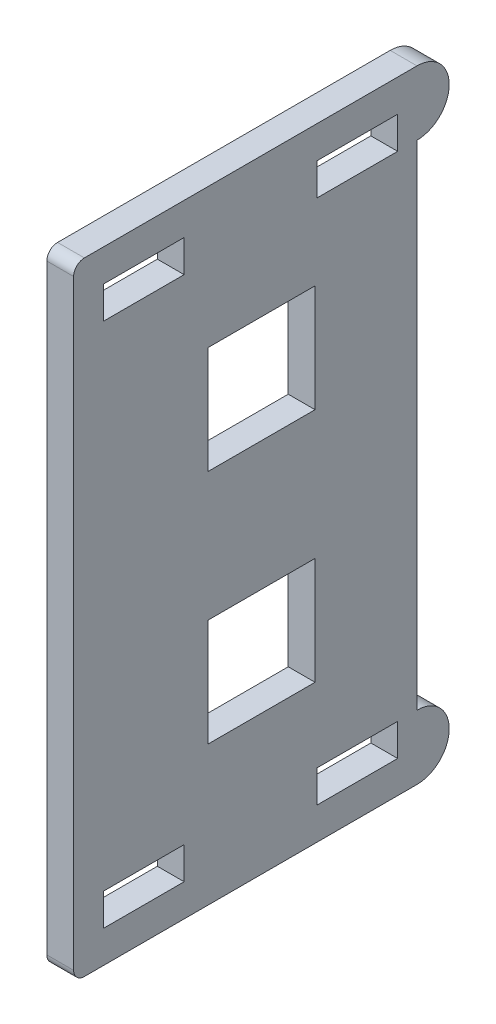
SolidWorks part; units mm, degrees
ref_plane "前视" through (0, 0, 0) normal (0, 0, 1) x (1, 0, 0)
ref_plane "上视" through (0, 0, 0) normal (0, 1, 0) x (1, 0, 0)
ref_plane "右视" through (0, 0, 0) normal (1, 0, 0) x (0, 0, -1)
sketch "草图2" plane through (0, 0, 0) normal (1, 0, 0) x (0, 0, -1)
  line L1 (-17.5, 29) -> (17.5, 29)
  line L2 (-17.5, 29) -> (-17.5, -29)
  line L3 (-17.5, -29) -> (17.5, -29)
  line L4 (17.5, 29) -> (17.5, -29)
  line L5 (-17.5, 29) -> (17.5, -29) construction
  line L6 (-17.5, -29) -> (17.5, 29) construction
  point P0 (0, 0)
  dimension "D1" = 58
  dimension "D2" = 35
extrude "凸台-拉伸1" add sketch "草图2" along normal blind 2.5
sketch "草图4" plane through (0, 0, 0) normal (-1, 0, 0) x (0, 0, 1)
  line L0 (-17.8855, 26) -> (19.6323, 26) construction
  line L1 (-17.5, 29) -> (17.5, 29) construction
  line L2 (-12.7, 26) -> (-5.2, 26)
  line L3 (-5.2, 26) -> (-5.2, 23)
  line L4 (-5.2, 23) -> (-12.7, 23)
  line L5 (-12.7, 23) -> (-12.7, 26)
  line L6 (-17.5, -29) -> (-17.5, 29) construction
  line L7 (7.2, 26) -> (14.7, 26)
  line L8 (14.7, 26) -> (14.7, 23)
  line L9 (14.7, 23) -> (7.2, 23)
  line L10 (7.2, 23) -> (7.2, 26)
  line L11 (17.5, 29) -> (17.5, -29) construction
  line L12 (0, 0) -> (-2.7087, 0) construction
  line L13 (-12.7, -23) -> (-12.7, -26)
  line L14 (7.2, -23) -> (7.2, -26)
  line L15 (-5.2, -26) -> (-5.2, -23)
  line L16 (14.7, -26) -> (14.7, -23)
  line L17 (14.7, -23) -> (7.2, -23)
  line L18 (7.2, -26) -> (14.7, -26)
  line L19 (-12.7, -26) -> (-5.2, -26)
  line L20 (-5.2, -23) -> (-12.7, -23)
  dimension "D1" = 3
  dimension "D2" = 4.8
  dimension "D3" = 3
  dimension "D4" = 7.5
  dimension "D5" = 7.5
  dimension "D6" = 3
  dimension "D7" = 2.8
extrude "切除-拉伸1" cut sketch "草图4" against normal through all
sketch "草图5" plane through (0, 0, 0) normal (-1, 0, 0) x (0, 0, 1)
  line L0 (-13.8103, 26) -> (-12.7631, 26) construction
  line L1 (-17.5, 29) -> (17.5, 29) construction
  line L2 (-14.5, 27.3502) -> (-14.5, 25.8843) construction
  line L3 (-17.5, -29) -> (-17.5, 29) construction
  line L4 (-11.0063, 0) -> (-20.4085, 0) construction
  line L5 (-14.5, 23) -> (-14.5, -23)
  line L6 (-14.5, 0) -> (-17.5, 0)
  line L7 (-17.5, -29) -> (-17.5, 29)
  line L8 (-14.5, 29) -> (-17.5, 29)
  line L9 (0, 0) -> (-4.681, 0) construction
  line L10 (-14.5, -29) -> (-17.5, -29)
  arc A0 (-14.5, 29) -> (-14.5, 23) centre (-14.5, 26) ccw
  arc A1 (-14.5, -29) -> (-14.5, -23) centre (-14.5, -26) cw
  line M9 (-17.5, 29) -> (-17.5, -29)
  line M10 (-17.5, -29) -> (17.5, -29)
  line M12 (17.5, 29) -> (-17.5, 29)
  dimension "D1" = 3
  dimension "D2" = 3
extrude "切除-拉伸2" cut sketch "草图5" against normal through all contours A0 M12 M9 | A0 L7 L6 L5 | A1 L5 L6 M9 | A1 L7 M10 | L7 L8 A0 L5 A1 L10 region at (0, -28.3299, -16.8299) region at (0, 28.3299, -16.8299) region at (0, 11.8314, -16.0226) region at (0, -11.8314, -16.0226)
sketch "草图7" plane through (0, 0, 0) normal (-1, 0, 0) x (0, 0, 1)
  line L0 (-12.7, -26) -> (-5.2, -26) construction
  line L1 (-5, -6) -> (5, -6)
  line L2 (-5, -6) -> (-5, -16)
  line L3 (-5, -16) -> (5, -16)
  line L4 (5, -6) -> (5, -16)
  line L5 (-14.5, 23) -> (-14.5, -23) construction
  line L6 (0, 0) -> (-3.3542, 0) construction
  line L7 (-5, 16) -> (5, 16)
  line L8 (5, 6) -> (5, 16)
  line L9 (-5, 6) -> (5, 6)
  line L10 (-5, 6) -> (-5, 16)
  dimension "D1" = 10
  dimension "D2" = 10
  dimension "D3" = 10
  dimension "D4" = 9.5
extrude "切除-拉伸3" cut sketch "草图7" against normal through all
fillet "圆角1" radius 1 2 edges at (1.25, -29, 17.5) (1.25, 29, 17.5)
